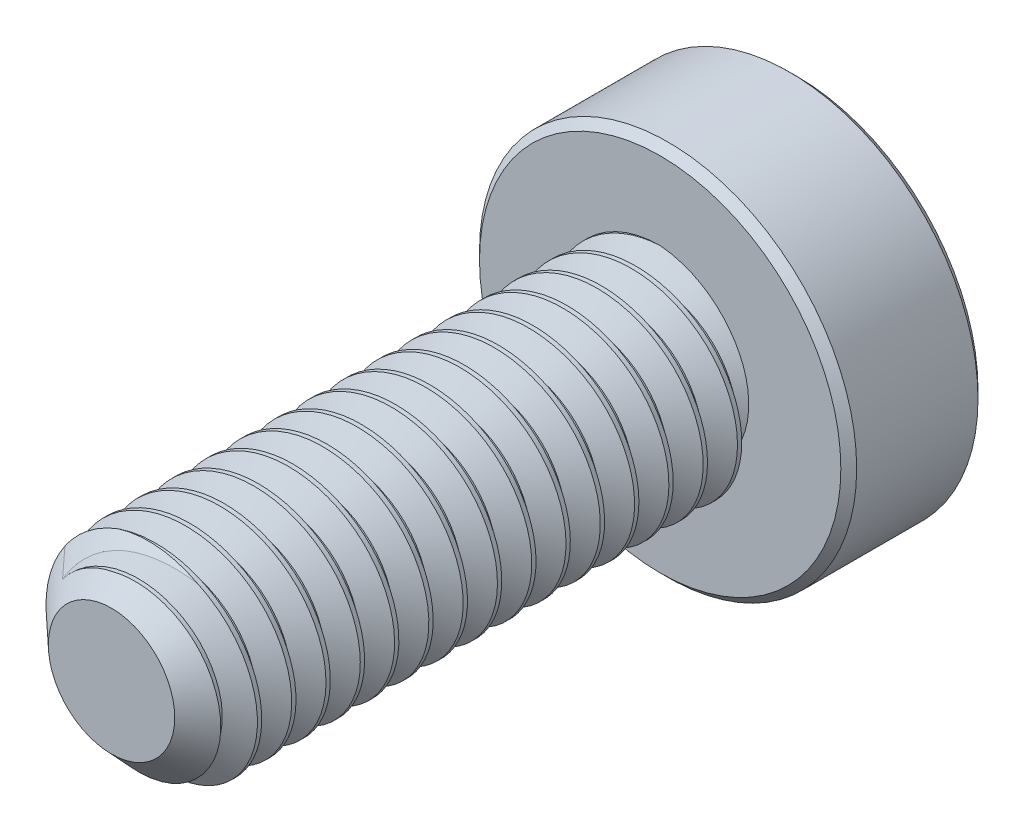
SolidWorks part; units mm, degrees
ref_plane "Front Plane" through (0, 0, 0) normal (0, 0, 1) x (1, 0, 0)
ref_plane "Top Plane" through (0, 0, 0) normal (0, 1, 0) x (1, 0, 0)
ref_plane "Right Plane" through (0, 0, 0) normal (1, 0, 0) x (0, 0, -1)
sketch "Sketch1" plane through (0, 0, 0) normal (0, 0, 1) x (1, 0, 0)
  circle A0 centre (0, 0) radius 1.5
  dimension "OD" = 3
extrude "Extrude1" add sketch "Sketch1" against normal blind 8
sketch "Sketch2" plane through (0, 0, 0) normal (0, 0, 1) x (1, 0, 0)
  circle A0 centre (0, 0) radius 1.5 construction
  circle A1 centre (0, 0) radius 1.5
curve "Helix/Spiral1" pitch 0.5 height 8.5 radius 1.5 centre (0, 0, 0) axis (0, 0, -1) start towards (0, 1, 0) parameters "pitch"=0.5
sketch "Sketch3" plane through (0, 0, 0) normal (1, 0, 0) x (0, 0, -1)
  line L0 (-0.4375, 1.5) -> (-0.25, 1.1752)
  line L1 (-0.25, 1.1752) -> (-0.1875, 1.1752)
  line L2 (-0.1875, 1.1752) -> (0, 1.5)
  line L3 (-0.4375, 1.5) -> (0, 1.5)
  line L4 (-0.2187, 1.5) -> (-0.2187, 1.1752) construction
  line L5 (-0.3438, 1.3376) -> (-0.0937, 1.3376) construction
  line L6 (0, 1.5) -> (0, -1.5) construction
  dimension "D1" = 0.0625
  dimension "D2" = 0.25
  dimension "D3" = 60
sweep "Cut-Sweep1" cut profiles "Sketch3" path "Helix/Spiral1"
sketch "Sketch4" plane through (0, 0, 0) normal (1, 0, 0) x (0, 0, -1)
  line L0 (0.5397, 1.5) -> (0, 0.9212)
  line L1 (0, 0.9212) -> (0, 1.5)
  line L2 (0.5397, 1.5) -> (0, 1.5)
  line L3 (-0.4375, 1.5) -> (0, 1.5) construction
  line L4 (0, 0) -> (7.0209, 0) construction
  dimension "D1" = 47
  dimension "D2" = 0.254
revolve "Cut-Revolve1" cut sketch "Sketch4" angle 360 about L4
sketch "Sketch5" plane through (0, 0, 0) normal (1, 0, 0) x (0, 0, -1)
  line L0 (8, -1.1822) -> (8, 1.0703) construction
  line L1 (8, 1.627) -> (28.1202, 1.627)
  line L2 (8, 1.627) -> (8, 0)
  line L3 (8, 0) -> (28, 0)
  line L4 (28, 1.2968) -> (28, 0)
  line L5 (28.1202, 1.627) -> (28, 1.2968)
  line L6 (0, 0) -> (9.9695, 0) construction
  point P3 (28, 1.627)
  point P10 (28, 1.627)
  dimension "D1" = 0.3302
  dimension "Thread min" = 28
  dimension "D2" = 0.127
  dimension "D3" = 20
revolve "partially thread" [suppressed] add sketch "Sketch5" angle 360 about L6
sketch "Sketch6" plane through (0, 0, -8) normal (0, 0, -1) x (-1, 0, 0)
  circle A0 centre (0, 0) radius 2.75
  dimension "head dia" = 5.5
extrude "Extrude2" add sketch "Sketch6" along normal blind 2
sketch "Sketch7" plane through (0, 0, -10) normal (0, 0, -1) x (-1, 0, 0)
  line L1 (0, 1.1547) -> (-1, 0.5774)
  line L2 (-1, 0.5774) -> (-1, -0.5774)
  line L3 (-1, -0.5774) -> (0, -1.1547)
  line L4 (0, -1.1547) -> (1, -0.5774)
  line L5 (1, -0.5774) -> (1, 0.5774)
  line L6 (1, 0.5774) -> (0, 1.1547)
  circle A0 centre (0, 0) radius 1 construction
  dimension "hex dia" = 2
extrude "Cut-Extrude1" cut sketch "Sketch7" against normal blind 1
sketch "Sketch8" plane through (0, 0, -10) normal (0, 0, -1) x (-1, 0, 0)
  circle A0 centre (0, 0) radius 1.1547
extrude "Cut-Extrude2" cut sketch "Sketch8" against normal blind 1 draft 45
chamfer "Chamfer1" distance 0.1155 angle 45 2 edges at (-2.75, 0, -10) (-2.75, 0, -8)
sketch "Sketch9" plane through (0, 0, 0) normal (1, 0, 0) x (0, 0, -1)
  line L0 (0, 1.5) -> (0, -1.5) construction
  line L1 (2.75, 1.5) -> (2.75, -1.5) construction
  dimension "D1" = 2.75
equation "\"D3@Helix/Spiral1\" = \"screw length@Extrude1\"+\"pitch@Helix/Spiral1\""
equation "\"D1@Sketch3\" = \"pitch@Helix/Spiral1\"*.125"
equation "\"D2@Sketch3\" = \"pitch@Helix/Spiral1\"*.5"
equation "\"D1@Cut-Extrude1\" = \"hex dia@Sketch7\" * .5"
equation "\"D1@Chamfer1\"  = \"head dia@Sketch6\" * .021"
equation "\"D1@Sketch9\" = \"pitch@Helix/Spiral1\"*5.5"
